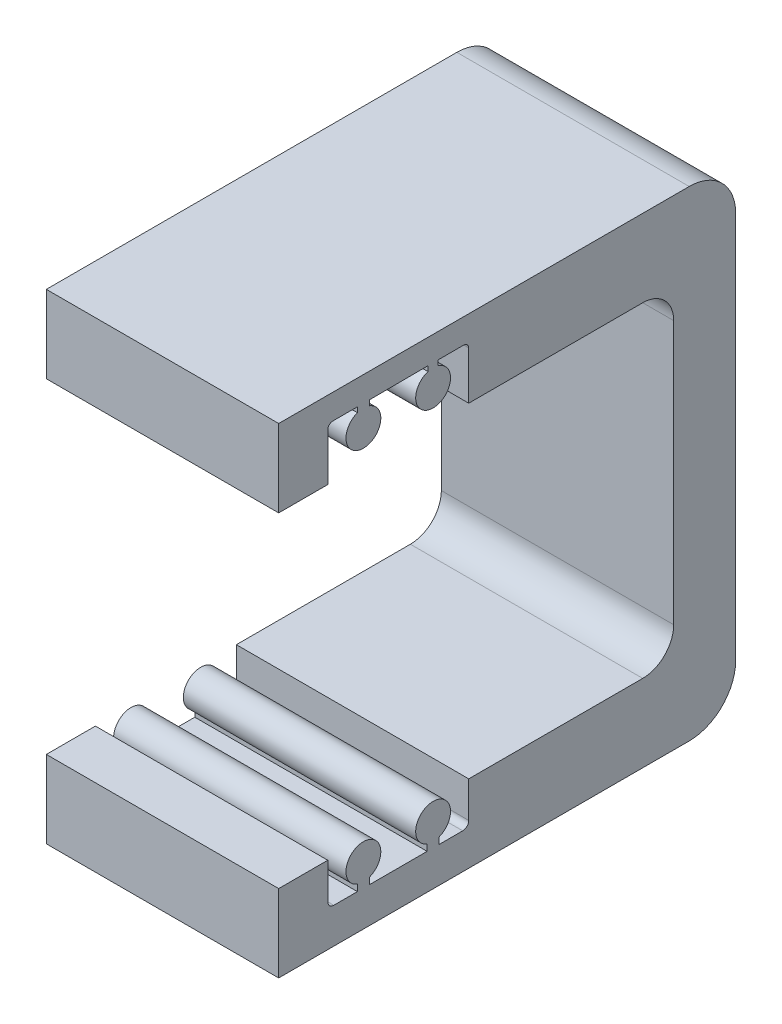
SolidWorks part; units mm, degrees
material "ABS"
ref_plane "Plano frontal" through (0, 0, 0) normal (0, 0, 1) x (1, 0, 0)
ref_plane "Plano superior" through (0, 0, 0) normal (0, 1, 0) x (1, 0, 0)
ref_plane "Plano direito" through (0, 0, 0) normal (1, 0, 0) x (0, 0, -1)
sketch "Esboço1" plane through (0, 0, 0) normal (0, 0, 1) x (1, 0, 0)
  line L0 (-15, 31) -> (-15, -31)
  line L1 (-15, -21) -> (15, -21)
  line L2 (-15, -21) -> (-15, 21)
  line L3 (-15, 21) -> (15, 21)
  line L4 (15, -21) -> (15, 21)
  line L5 (-15, -21) -> (15, 21) construction
  line L6 (-15, 21) -> (15, -21) construction
  line L7 (-15, -31) -> (15, -31)
  line L8 (15, -31) -> (15, 31)
  line L9 (15, 31) -> (-15, 31)
  point P0 (0, 0)
  point P10 (-15, 0)
  dimension "D1" = 42
  dimension "D2" = 30
  dimension "D3" = 10
extrude "Ressalto-extrusão1" add sketch "Esboço1" along normal blind 59 contours L8 L9 L0 L3 | L7 L8 L1 L0 region at (0, 26, 0) region at (0, -26, 0)
sketch "Esboço2" plane through (0, 0, 0) normal (0, 0, -1) x (-1, 0, 0)
  line L0 (15, -21) -> (-15, -21) construction
  line L1 (15, 31) -> (15, -31) construction
  line L2 (15, 21) -> (-15, 21) construction
  line L3 (-15, -21) -> (-15, 21) construction
  line L4 (15, -21) -> (-15, -21)
  line L5 (15, 31) -> (15, -31)
  line L6 (15, 21) -> (-15, 21)
  line L7 (-15, -21) -> (-15, 21)
  line L8 (-15, 21) -> (-15, 31)
  line L9 (-15, 31) -> (15, 31)
  line L10 (-15, -21) -> (-15, -31)
  line L11 (-15, -31) -> (15, -31)
  line L12 (15, -21) -> (-15, -21)
  line L13 (-15, 21) -> (15, 21)
  line L14 (15, -21) -> (-15, -21)
  line M2 (-15, 21) -> (15, 21)
extrude "Ressalto-extrusão2" add sketch "Esboço2" against normal blind 8 contours L7 L4 L5 M2 region at (0, 0, 0)
sketch "Esboço3" plane through (-15, 0, 0) normal (-1, 0, 0) x (0, 0, 1)
  line L0 (31.2729, 21) -> (33.5, 21)
  line L1 (59, 21) -> (8, 21) construction
  line L2 (34.4643, 21) -> (34.4643, 27.1808)
  line L3 (38.4075, 27.8215) -> (38.4075, 27.1622)
  line L4 (39.7211, 27.8215) -> (39.7211, 27.1622)
  line L6 (0, 0) -> (64.8544, 0) construction
  line L7 (47.295, 27.1246) -> (47.295, 27.7839)
  line L8 (48.8337, 27.1246) -> (48.8337, 27.7839)
  line L9 (52.5643, 26.27) -> (52.5643, 20.7683) construction
  line L10 (52.5643, 21) -> (54.6977, 21)
  line L11 (33.5, 21) -> (52.5643, 21)
  line L13 (35.105, 27.8215) -> (38.1075, 27.8215)
  line L14 (38.1075, 27.8215) -> (40.0211, 27.8215)
  line L15 (40.0211, 27.8215) -> (48.8534, 27.7758)
  line L16 (48.8534, 27.7758) -> (48.8337, 27.7839)
  line L17 (48.8337, 27.7839) -> (52.0143, 27.7839)
  line L18 (52.6643, 27.1338) -> (52.6643, 21)
  line L19 (0, 31) -> (0, -31) construction
  line L20 (44.3337, -27.7122) -> (44.3337, -28.817) construction
  line L21 (52.6643, -25.6493) -> (52.6643, -20.77)
  line L22 (49.2154, -26.4238) -> (51.8898, -26.4238)
  line L23 (48.5337, -26.4238) -> (49.2154, -26.4238)
  line L24 (40.1337, -26.4238) -> (48.5337, -26.4238)
  line L25 (37.995, -26.4238) -> (40.1337, -26.4238)
  line L26 (35.2389, -26.4238) -> (37.995, -26.4238)
  line L27 (34.4643, -20.7704) -> (34.4643, -25.6493)
  line L28 (34.5, -20.77) -> (52.5643, -20.77)
  line L29 (52.5643, -20.77) -> (54.6977, -20.77)
  line L30 (47.295, -25.5846) -> (47.295, -26.4238)
  line L31 (48.8337, -27.7122) -> (48.8337, -25.5846)
  line L32 (39.8337, -26.4238) -> (39.8337, -25.5846)
  line L33 (38.295, -26.4238) -> (38.295, -25.5846)
  line L34 (34.4643, -20.7704) -> (34.5, -20.77)
  line L35 (31.2729, -20.77) -> (34.5, -20.77)
  line L36 (34.5643, 20.7683) -> (34.5643, 26.27) construction
  line L37 (34.5643, -19.2283) -> (34.5643, -24.73) construction
  line L38 (34.4643, -20.7704) -> (34.5, -20.77)
  line L39 (52.6643, -20.77) -> (52.5643, -20.77)
  line L40 (46.995, -25.73) -> (46.995, -26.4238) construction
  line L41 (49.1337, -25.73) -> (49.1337, -26.4238) construction
  line L42 (40.1337, -25.73) -> (40.1337, -26.4238) construction
  line L43 (37.995, -25.73) -> (37.995, -26.4238) construction
  arc A0 (38.4075, 27.1622) -> (39.7211, 27.1622) centre (39.0643, 25.0102) ccw
  arc A1 (47.295, 27.1246) -> (48.8337, 27.1246) centre (48.0643, 25.0102) ccw
  arc A2 (51.8898, -26.4238) -> (52.6643, -25.6493) centre (51.8898, -25.6493) ccw
  arc A3 (34.4643, -25.6493) -> (35.2389, -26.4238) centre (35.2389, -25.6493) ccw
  arc A4 (35.105, 27.8215) -> (34.4643, 27.1622) centre (35.1143, 27.1715) ccw
  arc A5 (52.0143, 27.7839) -> (52.6643, 27.1338) centre (52.0143, 27.1338) cw
  arc A7 (38.295, -25.5846) -> (39.8337, -25.5846) centre (39.0643, -23.4702) cw
  arc A8 (48.8337, -25.5846) -> (47.295, -25.5846) centre (48.0643, -23.4702) ccw
  point P11 (48.0643, -23.4702)
  point P19 (49.1337, 27.27)
  point P20 (46.995, 27.27)
  point P78 (39.0643, -23.4702)
  point P88 (37.995, -26.0769)
  line M13 (59, -21) -> (8, -21)
  line M15 (8, 21) -> (59, 21)
  dimension "D2" = 4.5
  dimension "D9" = 4.5
  dimension "D10" = 0.1
  dimension "D11" = 0.1
  dimension "D12" = 2.25
  dimension "D3" = 0.3
  dimension "D4" = 0.3
  dimension "D1" = 0.1
  dimension "D5" = 0.1
  dimension "D6" = 0.3
  dimension "D7" = 0.3
  dimension "D8" = 0.3
extrude "Corte-extrusão1" cut sketch "Esboço3" against normal through all contours A8 L31 L23 L22 A2 L21 L34 L27 A3 L26 L25 L33 A7 L32 L24 L30 M13 | A5 L17 L16 L15 L8 A1 L7 L14 L4 A0 L3 L13 A4 L2 L0 L18 M15 region at (-15, 24.1231, 43.5432) region at (-15, -23.7376, 43.5643)
sketch "Esboço4" plane through (-15, 0, 0) normal (-1, 0, 0) x (0, 0, 1)
  line L0 (47.295, 27.7839) -> (48.8534, 27.7758)
  line L1 (48.8534, 27.7758) -> (48.8534, 27.1173)
  line L3 (47.2916, 27.1234) -> (47.295, 27.7839)
  line L4 (38.4075, 27.8215) -> (38.4075, 27.1622)
  line L6 (39.7211, 27.1622) -> (39.7211, 27.8215)
  line L7 (39.7211, 27.8215) -> (38.4075, 27.8215)
  arc A0 (38.4075, 27.1622) -> (39.7211, 27.1622) centre (39.0643, 25.0102) ccw
  arc A1 (47.2916, 27.1234) -> (48.8534, 27.1173) centre (48.0643, 25.0102) ccw
extrude "Corte-extrusão2" cut sketch "Esboço4" against normal blind 4
fillet "Filete1" radius 4 2 edges at (0, 21, 8) (0, -21, 8)
sketch "Esboço5" plane through (0, 0, 0) normal (0, 0, -1) x (-1, 0, 0)
  line L0 (-15, 0) -> (15, 0) construction
  line L4 (-15, 31) -> (-15, -31)
  line L5 (-15, -31) -> (15, -31)
  line L6 (15, -31) -> (15, 31)
  line L7 (15, 31) -> (-15, 31)
  line L8 (-15, 31) -> (-15, -31)
  line L9 (-15, -31) -> (15, -31)
  line L10 (15, -31) -> (15, 31)
  line L11 (15, 31) -> (-15, 31)
  circle A0 centre (0, -12) radius 2.5
  circle A1 centre (0, 12) radius 2.5
  dimension "D2" = 5
  dimension "D3" = 15
  dimension "D4" = 12
  dimension "D1" = 0
extrude "Corte-extrusão3" cut sketch "Esboço5" against normal blind 5 contours A1 | A0
fillet "Filete2" radius 6 2 edges at (0, -31, 0) (0, 31, 0)
